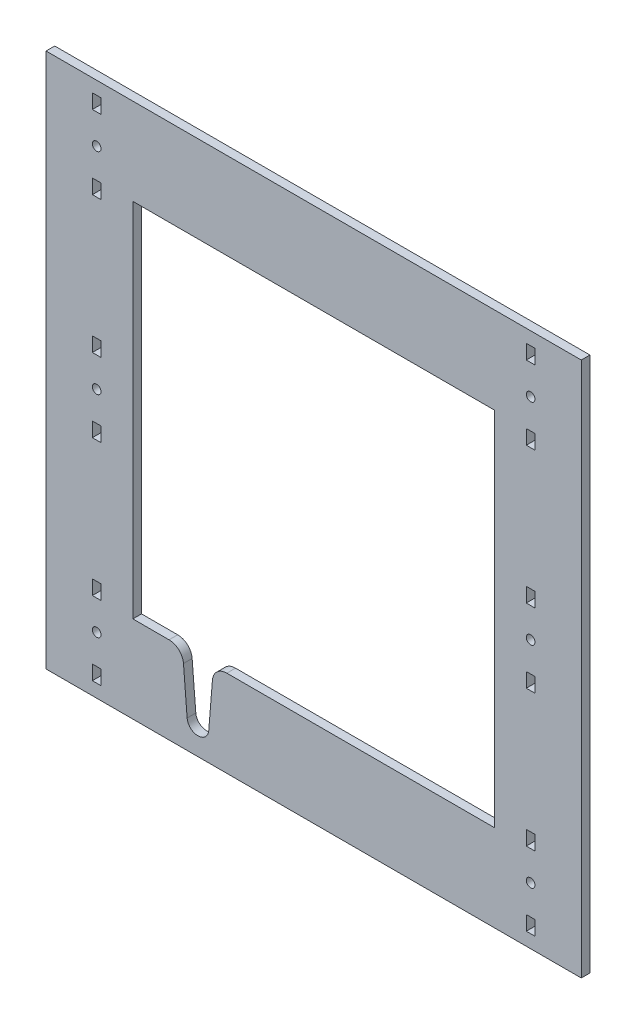
SolidWorks part; units mm, degrees
ref_plane "Front Plane" through (0, 0, 0) normal (0, 0, 1) x (1, 0, 0)
ref_plane "Top Plane" through (0, 0, 0) normal (0, 1, 0) x (1, 0, 0)
ref_plane "Right Plane" through (0, 0, 0) normal (1, 0, 0) x (0, 0, -1)
sketch "Sketch1" plane through (0, 0, 0) normal (0, 0, 1) x (1, 0, 0)
  line L0 (185, 185) -> (-185, -185) construction
  line L1 (-185, 185) -> (185, 185)
  line L2 (-185, 185) -> (-185, -185)
  line L3 (-185, -185) -> (185, -185)
  line L4 (185, 185) -> (185, -185)
  line L5 (-125, 125) -> (125, -125) construction
  line L6 (-125, 125) -> (125, 125)
  line L7 (-125, 125) -> (-125, -125)
  line L8 (-125, -125) -> (-99.9679, -125)
  line L9 (125, 125) -> (125, -125)
  line L10 (-150, 185) -> (-150, 176) construction
  line L11 (0, 185) -> (0, -185) construction
  line L12 (-150, 166) -> (-150, 145.5) construction
  line L13 (-153, 176) -> (-147, 176)
  line L14 (-153, 176) -> (-153, 166)
  line L15 (-153, 166) -> (-147, 166)
  line L16 (-147, 176) -> (-147, 166)
  line L17 (-150, 145.5) -> (-150, 125) construction
  line L18 (-150, 115) -> (-150, 30.5) construction
  line L19 (-153, 125) -> (-147, 125)
  line L20 (-153, 125) -> (-153, 115)
  line L21 (-153, 115) -> (-147, 115)
  line L22 (-147, 125) -> (-147, 115)
  line L23 (-150, 0) -> (-150, 20.5) construction
  line L24 (-153, 30.5) -> (-147, 30.5)
  line L25 (-153, 30.5) -> (-153, 20.5)
  line L26 (-153, 20.5) -> (-147, 20.5)
  line L27 (-147, 30.5) -> (-147, 20.5)
  line L28 (-150, 0) -> (-150, -20.5) construction
  line L29 (-150, -30.5) -> (-150, -115) construction
  line L30 (-153, -20.5) -> (-147, -20.5)
  line L31 (-153, -20.5) -> (-153, -30.5)
  line L32 (-153, -30.5) -> (-147, -30.5)
  line L33 (-147, -20.5) -> (-147, -30.5)
  line L34 (-150, -125) -> (-150, -145.5) construction
  line L35 (-153, -115) -> (-147, -115)
  line L36 (-153, -115) -> (-153, -125)
  line L37 (-153, -125) -> (-147, -125)
  line L38 (-147, -115) -> (-147, -125)
  line L39 (-150, -145.5) -> (-150, -166) construction
  line L40 (-150, -176) -> (-150, -185) construction
  line L41 (-153, -166) -> (-147, -166)
  line L42 (-153, -166) -> (-153, -176)
  line L43 (-153, -176) -> (-147, -176)
  line L44 (-147, -166) -> (-147, -176)
  line L45 (153, -176) -> (147, -176)
  line L46 (147, -166) -> (147, -176)
  line L47 (153, -166) -> (147, -166)
  line L48 (153, -166) -> (153, -176)
  line L49 (147, -115) -> (147, -125)
  line L50 (153, -125) -> (147, -125)
  line L51 (153, -115) -> (153, -125)
  line L52 (153, -115) -> (147, -115)
  line L53 (153, -30.5) -> (147, -30.5)
  line L54 (147, -20.5) -> (147, -30.5)
  line L55 (153, -20.5) -> (153, -30.5)
  line L56 (153, -20.5) -> (147, -20.5)
  line L57 (153, 20.5) -> (147, 20.5)
  line L58 (147, 30.5) -> (147, 20.5)
  line L59 (153, 30.5) -> (147, 30.5)
  line L60 (153, 30.5) -> (153, 20.5)
  line L61 (153, 115) -> (147, 115)
  line L62 (147, 125) -> (147, 115)
  line L63 (153, 125) -> (153, 115)
  line L64 (153, 125) -> (147, 125)
  line L65 (147, 176) -> (147, 166)
  line L66 (153, 166) -> (147, 166)
  line L67 (153, 176) -> (147, 176)
  line L68 (153, 176) -> (153, 166)
  line L69 (-80, -165) -> (-80, -185) construction
  line L70 (-90.7394, -125) -> (-69.2606, -125) construction
  line L71 (-90, -134.1988) -> (-87.4759, -165.6009)
  line L72 (-72.5241, -165.6009) -> (-70, -134.1988)
  line L73 (-80, -165) -> (-80, -125) construction
  line L74 (-60.0321, -125) -> (125, -125)
  line L75 (-90, -134.1988) -> (-70, -134.1988) construction
  circle A0 centre (-150, 145.5) radius 3
  circle A1 centre (-150, 0) radius 3
  circle A2 centre (-150, -145.5) radius 3
  circle A3 centre (150, -145.5) radius 3
  circle A4 centre (150, 0) radius 3
  circle A5 centre (150, 145.5) radius 3
  arc A6 (-87.4759, -165.6009) -> (-72.5241, -165.6009) centre (-80, -165) ccw
  arc A7 (-99.9679, -125) -> (-90, -134.1988) centre (-99.9679, -135) cw
  arc A8 (-70, -134.1988) -> (-60.0321, -125) centre (-60.0321, -135) cw
  point P27 (-147, -171)
  point P58 (147, -171)
  dimension "D3" = 6
  dimension "D5" = 6
  dimension "D10" = 10
  dimension "D12" = 7.5
  dimension "D13" = 10
  dimension "D1" = 370
  dimension "D2" = 250
  dimension "D4" = 10
  dimension "D6" = 9
  dimension "D7" = 41
  dimension "D8" = 35
  dimension "D9" = 105
  dimension "D11" = 20
  dimension "D14" = 20
extrude "Boss-Extrude1" add sketch "Sketch1" along normal mid plane 6
